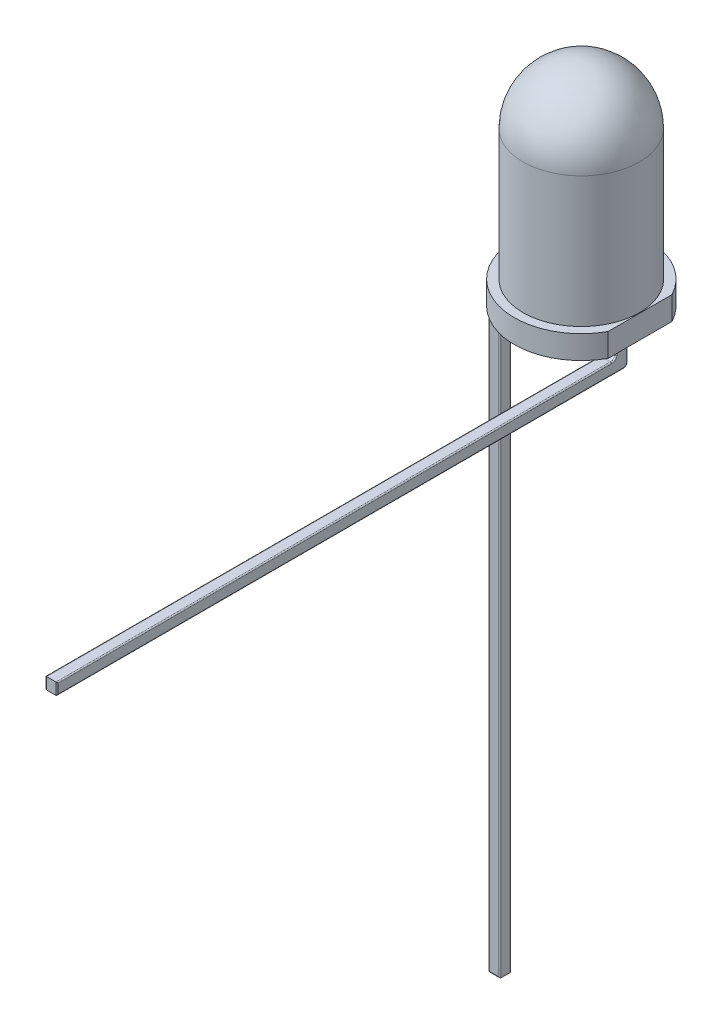
SolidWorks part; units mm, degrees
ref_plane "Front Plane" through (0, 0, 0) normal (0, 0, 1) x (1, 0, 0)
ref_plane "Top Plane" through (0, 0, 0) normal (0, 1, 0) x (1, 0, 0)
ref_plane "Right Plane" through (0, 0, 0) normal (1, 0, 0) x (0, 0, -1)
sketch "Sketch1" plane through (0, 0, 0) normal (0, 1, 0) x (1, 0, 0)
  circle A0 centre (0, 0) radius 2.875
  dimension "D1" = 5.75
extrude "Boss-Extrude1" add sketch "Sketch1" along normal blind 1
sketch "Sketch2" plane through (0, 1, 0) normal (0, 1, 0) x (1, 0, 0)
  circle A0 centre (0, 0) radius 2.5
  dimension "D1" = 5
extrude "Boss-Extrude2" add sketch "Sketch2" along normal blind 5.6
dome "Dome1" faces to dome 1 distance 2.5 reverse direction no elliptical dome no face at (0, 6.6, 2.5) parameters "D1"=2.5
sketch "Sketch3" plane through (0, 1, 0) normal (0, 1, 0) x (1, 0, 0)
  line L0 (2.525, 1.3748) -> (2.525, -1.3748)
  line L1 (2.525, -1.3748) -> (3.5652, -1.3748)
  line L2 (3.5652, -1.3748) -> (3.5652, 1.3748)
  line L3 (3.5652, 1.3748) -> (2.525, 1.3748)
  circle A0 centre (0, 0) radius 2.875 construction
  point P4 (-2.875, 0)
  dimension "D1" = 5.4
extrude "Cut-Extrude1" cut sketch "Sketch3" against normal blind 5.6
sketch "Sketch4" plane through (0, 0, 0) normal (0, -1, 0) x (1, 0, 0)
  line L1 (1.25, -0.25) -> (1.75, -0.25)
  line L2 (1.25, -0.25) -> (1.25, 0.25)
  line L3 (1.25, 0.25) -> (1.75, 0.25)
  line L4 (1.75, -0.25) -> (1.75, 0.25)
  line L5 (1.25, -0.25) -> (1.75, 0.25) construction
  line L6 (1.25, 0.25) -> (1.75, -0.25) construction
  line L7 (-1.75, 0.25) -> (-1.25, 0.25)
  line L8 (-1.75, 0.25) -> (-1.75, -0.25)
  line L9 (-1.75, -0.25) -> (-1.25, -0.25)
  line L10 (-1.25, 0.25) -> (-1.25, -0.25)
  line L11 (-1.75, 0.25) -> (-1.25, -0.25) construction
  line L12 (-1.75, -0.25) -> (-1.25, 0.25) construction
  point P0 (1.5, 0)
  point P5 (-1.5, 0)
  dimension "D1" = 0.5
  dimension "D2" = 0.5
  dimension "D3" = 1.5
  dimension "D4" = 0.5
  dimension "D5" = 0.5
  dimension "D6" = 1.5
extrude "Boss-Extrude3" add sketch "Sketch4" along normal blind 1.5
sketch "Sketch5" plane through (-1.75, 0, 0) normal (-1, 0, 0) x (0, 0, 1)
  line L0 (-0.25, -1.5) -> (-0.25, 0) construction
  line L1 (-0.25, -1) -> (0.25, -1)
  line L2 (-0.25, -1) -> (-0.25, -1.5)
  line L3 (-0.25, -1.5) -> (0.25, -1.5)
  line L4 (0.25, -1) -> (0.25, -1.5)
  line L5 (-0.25, -1) -> (0.25, -1.5) construction
  line L6 (-0.25, -1.5) -> (0.25, -1) construction
  line L7 (0.25, -1.5) -> (-0.25, -1.5) construction
  point P0 (0, -1.25)
  dimension "D1" = 0.5
  dimension "D2" = 0.5
extrude "Boss-Extrude4" add sketch "Sketch5" along normal blind 2
sketch "Sketch6" plane through (0, -1.5, 0) normal (0, -1, 0) x (1, 0, 0)
  line L0 (-3.75, -0.25) -> (-1.25, -0.25) construction
  line L2 (-3.75, 0.25) -> (-3.25, 0.25)
  line L3 (-3.75, 0.25) -> (-3.75, -0.25)
  line L4 (-3.75, -0.25) -> (-3.25, -0.25)
  line L5 (-3.25, 0.25) -> (-3.25, -0.25)
  dimension "D1" = 0.5
extrude "Boss-Extrude5" add sketch "Sketch6" along normal blind 25
sketch "Sketch7" plane through (0, 0, 0.25) normal (0, 0, 1) x (1, 0, 0)
  line L0 (1.75, -1.5) -> (1.75, 0) construction
  line L1 (1.25, -1.5) -> (1.75, -1.5)
  line L2 (1.25, -1.5) -> (1.25, -1)
  line L3 (1.25, -1) -> (1.75, -1)
  line L4 (1.75, -1.5) -> (1.75, -1)
  dimension "D1" = 0.5
extrude "Boss-Extrude6" add sketch "Sketch7" along normal blind 24
fillet "Fillet1" radius 0.2 6 edges at (-1.75, -1, 0) (-3.75, -1, 0) (-1.25, -1.5, 0) (1.5, -1.5, -0.25) (1.5, -1, 0.25)
fillet "Fillet2" radius 0.05 44 edges at (1.5, 0, 0.25) (1.5, 0, -0.25) (-1.75, 0, 0) (-1.25, 0, 0) (-3.5, -26.5, -0.25) (-3.1914, -1.5586, -0.25) (-1.3086, -1.4414, -0.25) (-1.25, -0.65, -0.25) (-1.5, 0, -0.25) (-1.75, -0.4, -0.25) (-1.8086, -0.9414, -0.25) (-2.75, -1, -0.25) (-3.6914, -1.0586, -0.25) (-3.75, -13.85, -0.25) (1.75, -1.25, 24.25) (1.75, -1, 12.35) (1.75, -0.9414, 0.3086) (1.75, -0.4, 0.25) (1.75, 0, 0) (1.75, -0.65, -0.25) (1.75, -1.4414, -0.1914) (1.75, -1.5, 12.1) (1.25, 0, 0) (1.25, -0.4, 0.25) (1.25, -0.9414, 0.3086) (1.25, -1, 12.35) (1.25, -1.25, 24.25) (1.25, -1.5, 12.1) (1.25, -1.4414, -0.1914) (1.25, -0.65, -0.25) (-1.8086, -0.9414, 0.25) (-1.75, -0.4, 0.25) (-1.5, 0, 0.25) (-1.25, -0.65, 0.25) (-1.3086, -1.4414, 0.25) (-3.1914, -1.5586, 0.25) (-3.5, -26.5, 0.25) (-3.75, -13.85, 0.25) (-3.6914, -1.0586, 0.25) (-2.75, -1, 0.25)
